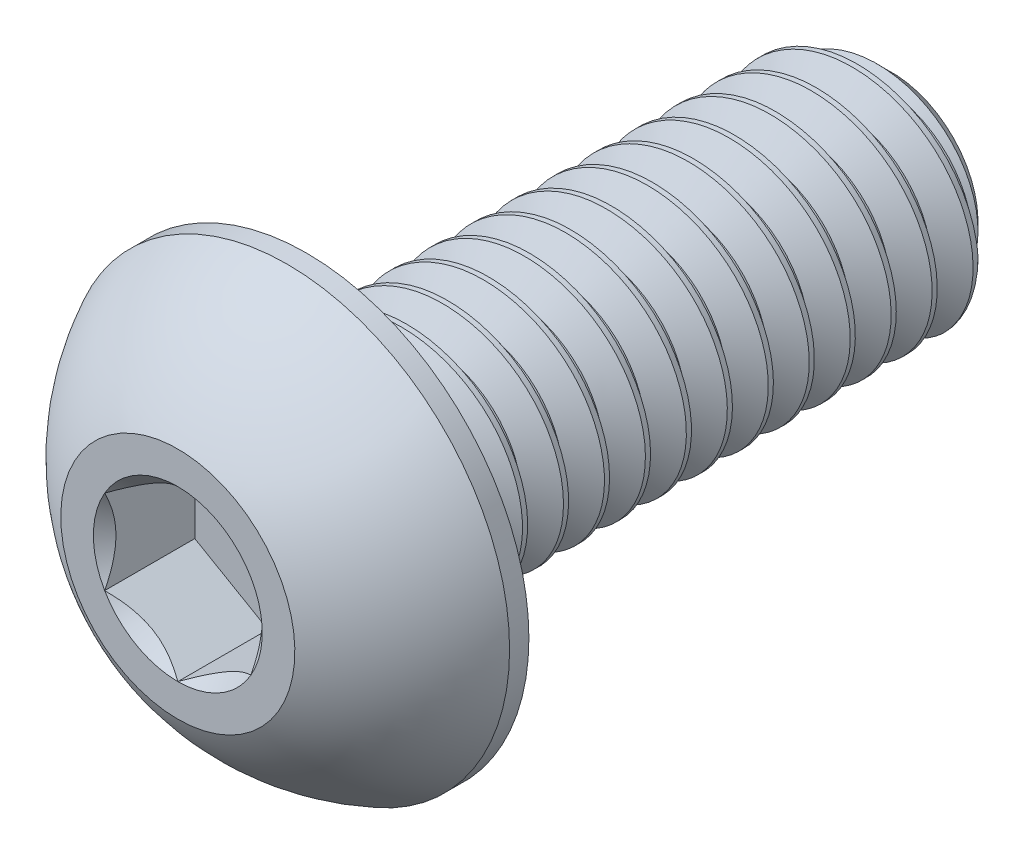
SolidWorks part; units mm, degrees
ref_plane "Front" through (0, 0, 0) normal (0, 0, 1) x (1, 0, 0)
ref_plane "Top" through (0, 0, 0) normal (0, 1, 0) x (1, 0, 0)
ref_plane "Right" through (0, 0, 0) normal (1, 0, 0) x (0, 0, -1)
sketch "Sketch1" plane through (0, 0, 0) normal (1, 0, 0) x (0, 0, -1)
  line L2 (-5, 2) -> (5, 2)
  line L3 (5, 2) -> (5, 0)
  line L4 (5, 0) -> (-5, 0)
  line L6 (-5.33, 3.8) -> (-5, 3.8) construction
  line L7 (5, 2) -> (5, -2) construction
  line L8 (-7.2, 0) -> (-5, 0) construction
  line L9 (-5, 3.8) -> (-5, -3.8) construction
  line L11 (-5, 2) -> (-5, 0)
  line L13 (-7.2, 1.25) -> (-7.2, -1.25) construction
  line L14 (-7.2, 1.25) -> (-7.2, 2) construction
  line L15 (4.9563, 2.0758) -> (5.3063, 1.4696) construction
  line L16 (5.3063, 1.4696) -> (5.6563, 2.0758) construction
  line L17 (5.6563, 2.0758) -> (4.9563, 2.0758) construction
  line L18 (5, 2) -> (5.6125, 2) construction
  line L19 (5.3063, 2.0758) -> (5.3063, 2) construction
  line L20 (5.3063, 2) -> (5.3063, 1.5453) construction
  line L21 (5.3063, 1.5453) -> (5.3063, 1.4696) construction
  line L22 (5.2625, 1.5453) -> (5.35, 1.5453)
  line L23 (4.9781, 2.0379) -> (5.6344, 2.0379)
  line L24 (5.35, 1.5453) -> (5.6344, 2.0379)
  line L25 (5.2625, 1.5453) -> (4.9781, 2.0379)
  line L26 (4.475, 2) -> (5, 1.475)
  arc A3 (-7.2, 2) -> (-5.33, 3.8) centre (-3.4736, 0) cw construction
  point P29 (5.3063, 2.0379)
  point P30 (3.25, -2)
  point P33 (0, 0)
  dimension "Thread Size" = 4
  dimension "D1" = 0.33
  dimension "Head Height" = 2.2
  dimension "Head Diameter" = 7.6
  dimension "Length" = 10
  dimension "Drive Size" = 2.5
  dimension "Thread Pitch" = 0.7
  dimension "D3" = 0.0875
  dimension "D2" = 0.525
  dimension "D4" = 45
  dimension "D5" = 1.75
sketch "Sketch10" plane through (0, 0, 0) normal (1, 0, 0) x (0, 0, -1)
  line L0 (4.475, 2) -> (5, 1.475) construction
  line L1 (4.475, 2) -> (5, 1.475)
  line L4 (5, 2) -> (-5, 2)
  line L5 (5, 0) -> (5, 2)
  line L6 (-5, 0) -> (5, 0)
  line L7 (-5, 2) -> (-5, 0)
  line L8 (4.475, 2) -> (-5, 2)
  line L9 (5, 0) -> (5, 1.475)
  line L10 (-5, 0) -> (5, 0)
  line L11 (-5, 2) -> (-5, 0)
  dimension "D1" = 0
revolve "Revolve3" add sketch "Sketch10" angle 360 about L8
sketch "Sketch7" plane through (0, 0, 0) normal (1, 0, 0) x (0, 0, -1)
  line L6 (-5.33, 3.8) -> (-5, 3.8) construction
  line L8 (-7.2, 0) -> (-5, 0) construction
  line L11 (-5, 3.8) -> (-5, -3.8) construction
  line L12 (-5.33, 3.8) -> (-5, 3.8)
  line L13 (-7.2, 0) -> (-5, 0)
  line L14 (-7.2, 1.25) -> (-7.2, -1.25) construction
  line L15 (-5, 3.8) -> (-5, 0)
  line L16 (-7.2, 2) -> (-7.2, 0)
  arc A2 (-5.33, 3.8) -> (-7.2, 2) centre (-3.4736, 0) ccw construction
  arc A3 (-5.33, 3.8) -> (-7.2, 2) centre (-3.4736, 0) ccw
revolve "Revolve2" add sketch "Sketch7" angle 360 mid plane about L13
sketch "Sketch5" plane through (0, 0, 7.2) normal (0, 0, 1) x (1, 0, 0)
  line L1 (1.25, -0.7217) -> (1.25, 0.7217)
  line L2 (1.25, 0.7217) -> (0, 1.4434)
  line L3 (0, 1.4434) -> (-1.25, 0.7217)
  line L4 (-1.25, 0.7217) -> (-1.25, -0.7217)
  line L5 (-1.25, -0.7217) -> (0, -1.4434)
  line L6 (0, -1.4434) -> (1.25, -0.7217)
  circle A0 centre (0, 0) radius 1.25 construction
extrude "Cut-Extrude2" cut sketch "Sketch5" against normal blind 1.54
sketch "Sketch6" plane through (0, 0, 7.2) normal (0, 0, 1) x (1, 0, 0)
  circle A0 centre (0, 0) radius 1.4434
extrude "Cut-Extrude3" cut sketch "Sketch6" against normal blind 1.54 draft 45
sketch "Sketch9" plane through (0, 0, 5) normal (0, 0, -1) x (-1, 0, 0)
  circle A0 centre (0, 0) radius 2 construction
  circle A4 centre (0, 0) radius 2
split "Split1" bodies to split 113 resulting bodies 123 124 split by face at (0, -3.8, 5)
sketch "Sketch11" plane through (0, 0, -5) normal (0, 0, -1) x (-1, 0, 0)
  circle A0 centre (0, 0) radius 2 construction
  circle A1 centre (0, 0) radius 2
curve "Helix/Spiral1" pitch 0.7 height 12.2 radius 2 centre (0, 0, -5) axis (0, 0, 1) start towards (0, 1, 0)
sketch "Sketch12" plane through (0, 0, 0) normal (1, 0, 0) x (0, 0, -1)
  line L0 (5.2625, 1.5453) -> (5.35, 1.5453) construction
  line L1 (5.35, 1.5453) -> (5.6344, 2.0379) construction
  line L2 (4.9781, 2.0379) -> (5.6344, 2.0379) construction
  line L3 (5.2625, 1.5453) -> (4.9781, 2.0379) construction
  line L4 (5.2625, 1.5453) -> (5.35, 1.5453)
  line L5 (5.35, 1.5453) -> (5.6344, 2.0379)
  line L6 (4.9781, 2.0379) -> (5.6344, 2.0379)
  line L7 (5.2625, 1.5453) -> (4.9781, 2.0379)
sweep "Cut-Sweep2" cut profiles "Sketch12" path "Helix/Spiral1" align with end faces yes
extrude "Boss-Extrude1" add sketch "Sketch9" along normal blind 10 draft 45
equation "\"D1@Cut-Extrude2\" = \"Head Height@Sketch1\" * .7"
equation "\"D1@Sketch1\" = \"Head Height@Sketch1\" * .15"
equation "\"D1@Cut-Extrude3\" = \"D1@Cut-Extrude2\""
equation "\"D3@Sketch1\" = \"Thread Pitch@Sketch1\" / 8"
equation "\"D2@Sketch1\" = \"Thread Pitch@Sketch1\" * 0.75"
equation "\"D3@Helix/Spiral1\" = \"Length@Sketch1\" + \"Head Height@Sketch1\""
equation "\"D4@Helix/Spiral1\" = \"Thread Pitch@Sketch1\""
equation "\"D5@Sketch1\" = \"Thread Pitch@Sketch1\" * 2.5"
